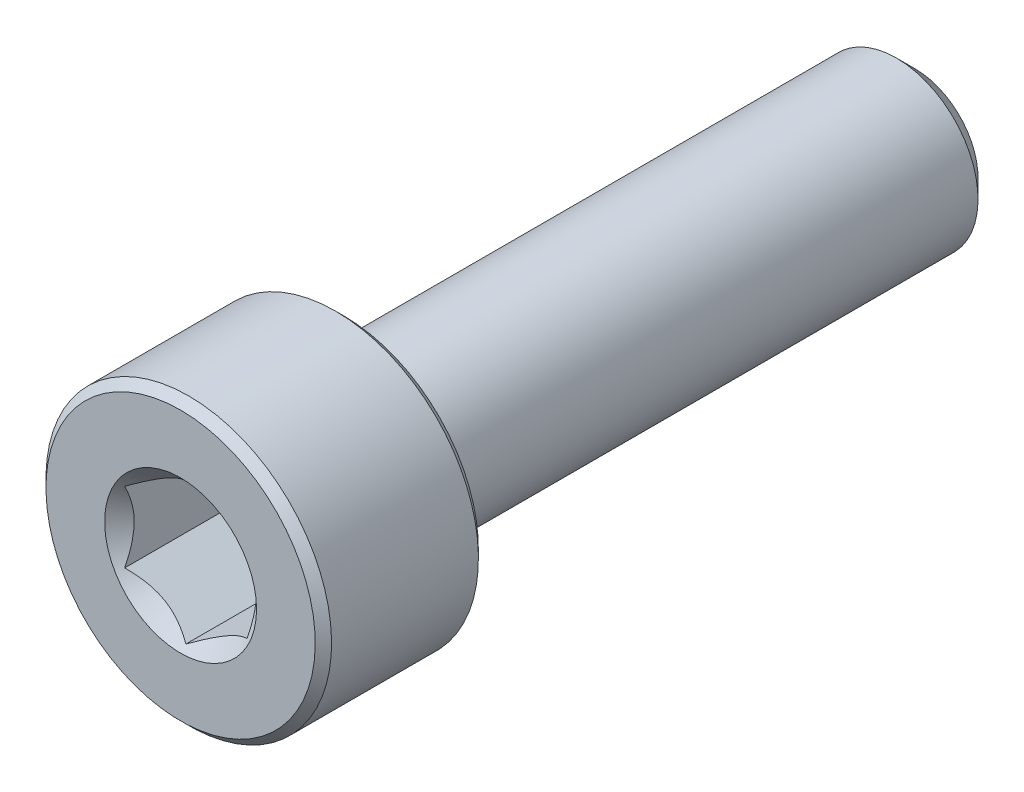
SolidWorks part; units mm, degrees
ref_plane "Front Plane" through (0, 0, 0) normal (0, 0, 1) x (1, 0, 0)
ref_plane "Top Plane" through (0, 0, 0) normal (0, 1, 0) x (1, 0, 0)
ref_plane "Right Plane" through (0, 0, 0) normal (1, 0, 0) x (0, 0, -1)
sketch "Sketch1" plane through (0, 0, 0) normal (1, 0, 0) x (0, 0, -1)
  line L0 (-9, 0) -> (9, 0) construction
  line L1 (9, 0) -> (9, 1.5453) construction
  line L2 (9, 1.5453) -> (8.5453, 2) construction
  line L3 (8.5453, 2) -> (8.475, 2) construction
  line L4 (8.475, 2) -> (-5, 2) construction
  line L5 (-5, 2) -> (-5, 3.5) construction
  line L6 (-5, 3.5) -> (-9, 3.5) construction
  line L7 (-9, 3.5) -> (-9, 0) construction
  line L8 (9, 1.5453) -> (9, 2) construction
  line L9 (8.9562, 2.0758) -> (9.3063, 1.4696) construction
  line L10 (9.3063, 1.4696) -> (9.6562, 2.0758) construction
  line L11 (9.6562, 2.0758) -> (8.9562, 2.0758) construction
  line L12 (9.3063, 2.0758) -> (9.3063, 2) construction
  line L13 (9.3063, 1.4696) -> (9.3063, 1.5453) construction
  line L14 (9.2625, 1.5453) -> (9.35, 1.5453) construction
  line L15 (9, 2) -> (9.6125, 2) construction
  line L16 (8.9781, 2.0379) -> (9.6344, 2.0379) construction
  line L17 (9, 0) -> (9, -2) construction
  line L18 (-5.2, 3.5) -> (-5, 3.3) construction
  line L19 (-8.8, 3.5) -> (-9, 3.3) construction
  line L20 (-5, 2) -> (-5, 0) construction
  line L21 (-5, 1) -> (-0.3333, 1) construction
  line L22 (-0.3333, 1) -> (4.3333, 1) construction
  line L23 (4.3333, 1) -> (9, 1) construction
  line L24 (-0.3333, 1) -> (-0.3333, 2) construction
  line L25 (-0.3333, 2) -> (-0.3333, 3.5) construction
  line L26 (4.3333, 1) -> (4.3333, 3.5) construction
  point P0 (-9, 1.5)
  point P3 (7.25, 2)
  point P4 (0, 0)
  point P18 (4.3333, 2)
  point P22 (9.3063, 1.5453)
  point P24 (8.475, 2)
  point P25 (9.3063, 2)
  point P28 (9.3063, 2.0379)
  point P29 (7.25, -2)
  point P30 (-0.3333, 2)
  point P31 (-7, 3.5)
  point P37 (-5.7, 3.5)
  point P38 (-8.7, 3.5)
  point P45 (-0.3333, 1)
  point P46 (4.3333, 1)
  dimension "D2" = 0.0875
  dimension "D7" = 0.2
  dimension "D8" = 0.2
  dimension "D9" = 0.2
  dimension "D10" = 0.1
  dimension "D11" = 0.5
  dimension "Drive Size" = 3
  dimension "Head Diameter" = 7
  dimension "Head Height" = 4
  dimension "Thread Pitch" = 0.7
  dimension "Thread Dia" = 4
  dimension "Length" = 14
  dimension "D12" = 0.525
  dimension "D4" = 1.75
  dimension "D3" = 45
sketch "Sketch2" plane through (0, 0, 0) normal (1, 0, 0) x (0, 0, -1)
  line L0 (-9, 0) -> (-9, 3.3)
  line L1 (-8.8, 3.5) -> (-5.2, 3.5)
  line L2 (-5, 3.3) -> (-5, 2.2)
  line L4 (8.5453, 2) -> (9, 1.5453)
  line L5 (9, 1.5453) -> (9, 0)
  line L6 (-5, 3.5) -> (-9, 3.5) construction
  line L7 (9, 0) -> (-9, 0)
  line L8 (-8.8, 3.5) -> (-9, 3.3) construction
  line L10 (-8.8, 3.5) -> (-9, 3.3)
  line L14 (-5.2, 3.5) -> (-5, 3.3) construction
  line L16 (-5.2, 3.5) -> (-5, 3.3)
  line L17 (-5, 2) -> (-5, 3.5) construction
  line L19 (-4.8, 2) -> (8.5453, 2)
  line L20 (8.475, 2) -> (-5, 2) construction
  arc A1 (-5, 2.2) -> (-4.8, 2) centre (-4.8, 2.2) ccw
  dimension "D3" = 0.2
revolve "Revolve1" add sketch "Sketch2" angle 360 about L7
sketch "Sketch3" plane through (0, 0, 9) normal (0, 0, 1) x (1, 0, 0)
  line L1 (1.5, -0.866) -> (1.5, 0.866)
  line L2 (1.5, 0.866) -> (0, 1.7321)
  line L3 (0, 1.7321) -> (-1.5, 0.866)
  line L4 (-1.5, 0.866) -> (-1.5, -0.866)
  line L5 (-1.5, -0.866) -> (0, -1.7321)
  line L6 (0, -1.7321) -> (1.5, -0.866)
  circle A0 centre (0, 0) radius 1.5 construction
  circle A1 centre (0, 0) radius 3.5 construction
  circle A2 centre (0, 0) radius 3.5 construction
  circle A3 centre (0, 0) radius 1.7321 construction
  point P13 (0, 0)
  dimension "D1" = 3.4641
extrude "Cut-Extrude1" cut sketch "Sketch3" against normal offset from surface (3 mm away) 1 up to face at (0, 3.3, 5)
sketch "Sketch4" plane through (0, 0, 9) normal (0, 0, 1) x (1, 0, 0)
  circle A0 centre (0, 0) radius 1.862
  dimension "D1" = 3.7239
extrude "Cut-Extrude2" cut sketch "Sketch4" against normal up to vertex (2 mm away) draft 45 up to point (0, 3.5, 7)
sketch "Sketch11" plane through (0, 0, 0) normal (1, 0, 0) x (0, 0, -1)
  line L0 (-9, 0) -> (9, 0) construction
  line L1 (-9, 0) -> (9, 0) construction
  line L2 (-2.375, 0) -> (-2.375, 2) construction
  line L3 (8.475, 2) -> (-5, 2) construction
  line L4 (6.375, 0) -> (6.375, 2) construction
  line L6 (9, 1.5453) -> (9, 2) construction
  point P2 (-2.375, 0)
  point P3 (6.375, 0)
  dimension "D1" = 2.625
  dimension "D2" = 2.625
sketch "Sketch6" [suppressed] plane through (0, 0, -9) normal (0, 0, -1) x (-1, 0, 0)
  circle A0 centre (0, 0) radius 2
curve "Helix/Spiral1" [suppressed] pitch 0.7 height 14.7 turns 21
sketch "Sketch10" [suppressed] plane through (0, 0, 0) normal (1, 0, 0) x (0, 0, -1)
  line L0 (-4.8, -3.5) -> (-4.8, 3.5)
  line L5 (-9, 0) -> (9, 0) construction
  line L6 (-4.8, 2) -> (-4.8, -2) construction
  point P3 (-4.8, 0)
split "Split1" [suppressed] bodies to split 106
sketch "Sketch7" [suppressed] plane through (0, 0, 0) normal (1, 0, 0) x (0, 0, -1)
  line L0 (8.9781, 2.0379) -> (9.6344, 2.0379)
  line L1 (9.6344, 2.0379) -> (9.35, 1.5453)
  line L2 (9.35, 1.5453) -> (9.2625, 1.5453)
  line L3 (9.2625, 1.5453) -> (8.9781, 2.0379)
sweep "Cut-Sweep1" [suppressed] cut profiles "Sketch7" path "Helix/Spiral1"
sketch "Sketch8" [suppressed] plane through (0, 0, 0) normal (1, 0, 0) x (0, 0, -1)
  line L0 (-5, 0) -> (-5, 2)
  line L1 (-4.8, -2) -> (-4.8, 2) construction
  line L2 (-5, 2) -> (-4.8, 2)
  line L4 (-4.8, 2) -> (-3.6453, 0)
  line L5 (-3.6453, 0) -> (-5, 0)
  line L6 (8.475, 2) -> (-5, 2) construction
  line L7 (-9, 0) -> (9, 0) construction
  dimension "D1" = 60
revolve "Revolve2" [suppressed] add sketch "Sketch8" angle 360 about L5
equation "\"D2@Sketch1\" = \"Thread Pitch@Sketch1\" / 8"
equation "\"D4@Helix/Spiral1\" = \"Thread Pitch@Sketch1\""
equation "\"D7@Sketch1\" = \"Head Height@Sketch1\" * .05"
equation "\"D8@Sketch1\"=\"D7@Sketch1\""
equation "\"D9@Sketch1\"=\"D7@Sketch1\""
equation "\"D10@Sketch1\"=\"D7@Sketch1\"/2"
equation "\"D11@Sketch1\"=\"D10@Sketch1\"*5"
equation "\"D4@Sketch1\"=\"Thread Pitch@Sketch1\"*2.5"
equation "\"D12@Sketch1\"=\"Thread Pitch@Sketch1\"*.75"
equation "\"D3@Helix/Spiral1\"=\"Length@Sketch1\"+\"Thread Pitch@Sketch1\""
equation "\"D3@Sketch2\"=\"Thread Dia@Sketch1\"*0.05"
equation "\"D1@Sketch11\"=\"Length@Sketch1\"*0.1875"
equation "\"D2@Sketch11\"=\"D1@Sketch11\""
equation "\"D1@Sketch4\"=\"D1@Sketch3\"*1.075"
